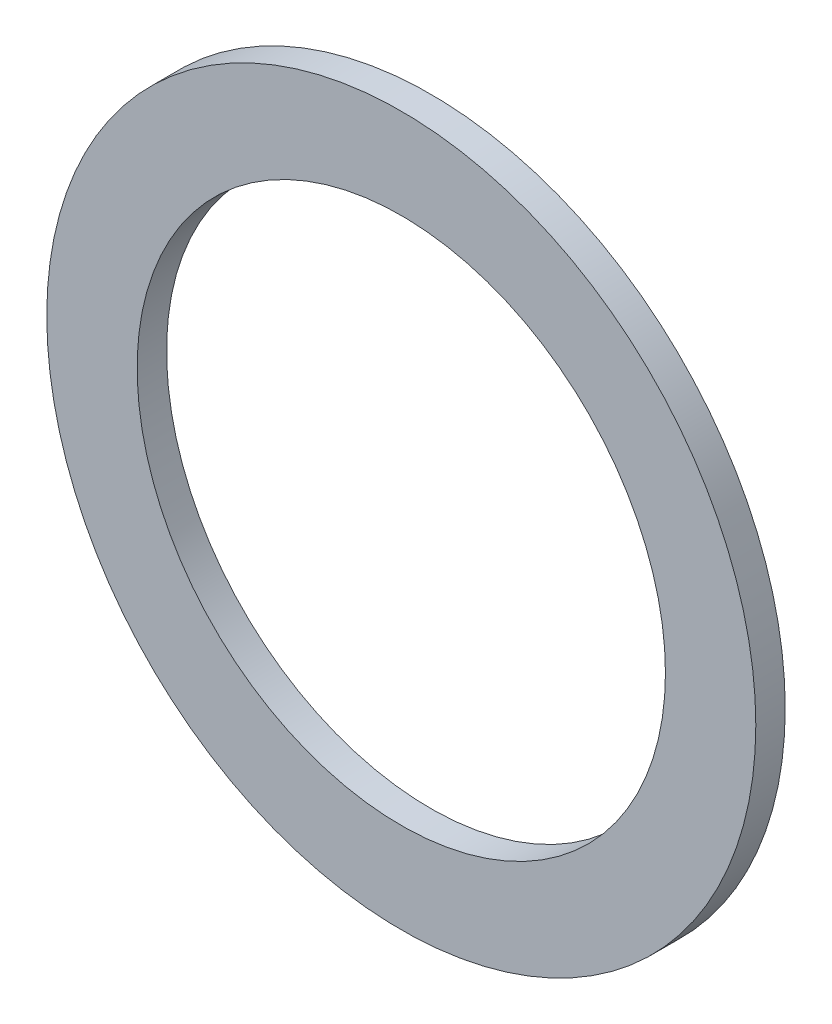
SolidWorks part; units mm, degrees
ref_plane "Front Plane" through (0, 0, 0) normal (0, 0, 1) x (1, 0, 0)
ref_plane "Top Plane" through (0, 0, 0) normal (0, 1, 0) x (1, 0, 0)
ref_plane "Right Plane" through (0, 0, 0) normal (1, 0, 0) x (0, 0, -1)
sketch "Sketch1" plane through (0, 0, 0) normal (0, 0, 1) x (1, 0, 0)
  circle A0 centre (0, 0) radius 38.25
  circle A1 centre (0, 0) radius 28.5
  dimension "D1" = 57
  dimension "D2" = 76.5
extrude "Boss-Extrude1" add sketch "Sketch1" along normal blind 3.175
